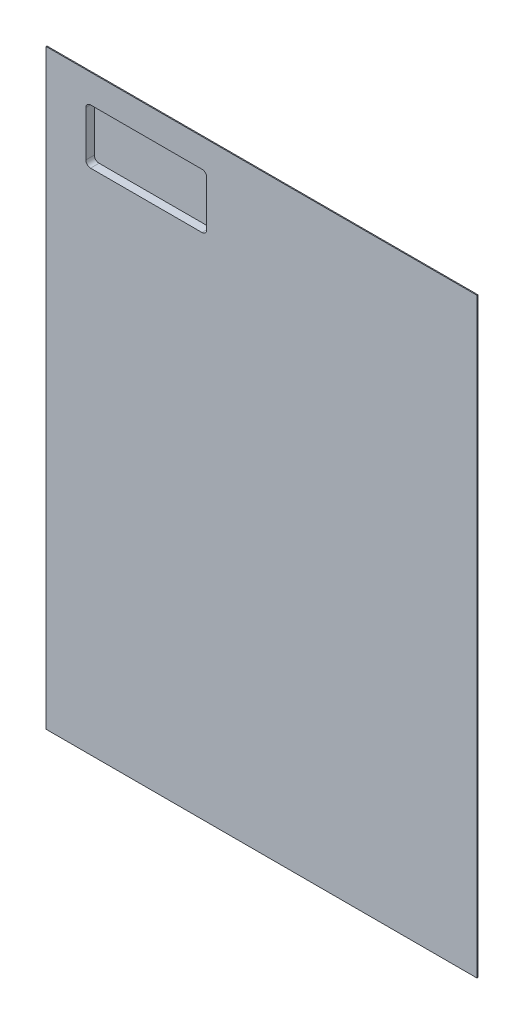
SolidWorks part; units mm, degrees
ref_plane "Front Plane" through (0, 0, 0) normal (0, 0, 1) x (1, 0, 0)
ref_plane "Top Plane" through (0, 0, 0) normal (0, 1, 0) x (1, 0, 0)
ref_plane "Right Plane" through (0, 0, 0) normal (1, 0, 0) x (0, 0, -1)
sketch "Sketch1" plane through (0, 0, 0) normal (0, 0, 1) x (1, 0, 0)
  line L1 (-228, 313) -> (228, 313)
  line L2 (-228, 313) -> (-228, -313)
  line L3 (-228, -313) -> (228, -313)
  line L4 (228, 313) -> (228, -313)
  line L5 (-228, 313) -> (228, -313) construction
  line L6 (-228, -313) -> (228, 313) construction
  point P0 (0, 0)
  dimension "D1" = 456
  dimension "D2" = 626
base flange "Base-Flange1" sketch "Sketch1" thickness 1 reverse thickness direction no parameters "D1"=0.7366
sketch "Sketch6" plane through (0, 0, 0) normal (0, 0, 1) x (1, 0, 0)
  line L0 (228, 313) -> (-228, 313) construction
  line L1 (-187, 284) -> (-57, 284)
  line L2 (-187, 284) -> (-187, 224)
  line L3 (-187, 224) -> (-57, 224)
  line L4 (-57, 284) -> (-57, 224)
  line L5 (-187, 284) -> (-57, 224) construction
  line L6 (-187, 224) -> (-57, 284) construction
  line L7 (-228, 313) -> (-228, -313) construction
  point P0 (-122, 254)
  dimension "D1" = 29
  dimension "D2" = 41
  dimension "D3" = 60
  dimension "D4" = 130
extrude "Boss-Extrude1" add sketch "Sketch6" against normal blind 10
sketch "Sketch7" plane through (0, 0, 0) normal (0, 0, 1) x (1, 0, 0)
  line L4 (-186, 283) -> (-58, 283)
  line L5 (-58, 283) -> (-58, 225)
  line L6 (-186, 225) -> (-58, 225)
  line L7 (-186, 283) -> (-186, 225)
  line L12 (-57, 284) -> (-57, 224) construction
  line L13 (-187, 224) -> (-57, 224) construction
  line L14 (-187, 284) -> (-187, 224) construction
  line L15 (-187, 284) -> (-57, 284) construction
  line L16 (-57, 284) -> (-57, 224) construction
  line L17 (-187, 224) -> (-57, 224) construction
  line L18 (-187, 284) -> (-187, 224) construction
  line L19 (-187, 284) -> (-57, 284) construction
  dimension "D1" = 1
extrude "Cut-Extrude2" cut sketch "Sketch7" against normal blind 1
shell "Shell2" thickness 1
fillet "Fillet1" radius 5 8 edges at (-57, 284, -5.5) (-57, 224, -5.5) (-187, 224, -5.5) (-187, 284, -5.5) (-186, 225, -4.5) (-186, 283, -4.5) (-58, 283, -4.5) (-58, 225, -4.5)
sketch "Bend-Lines1" plane through (0, 0, 0) normal (0, 1, 0) x (1, 0, 0)
sketch "Bounding-Box1" plane through (0, 0, 0) normal (0, 1, 0) x (1, 0, 0)
sheet metal parameters "Sheet-Metal1" thickness 1 parameters "D1"=0.7366
flat pattern "Flat-Pattern1"
sketch "Bend-Lines2" plane through (0, 0, 0) normal (0, 1, 0) x (1, 0, 0)
sketch3d "Bounding-Box2"
  line L0 (228, 313, 0) -> (228, -313, 0) construction
  line L1 (-228, 313, 0) -> (-228, -313, 0) construction
  line L2 (228, 313, 0) -> (-228, 313, 0) construction
  line L3 (228, -313, 0) -> (-228, -313, 0) construction
sheet metal parameters "Sheet-Metal2" thickness 1 parameters "D1"=0.7366
flat pattern "Flat-Pattern1"
sketch "Bend-Lines2" plane through (0, 0, 0) normal (0, 1, 0) x (1, 0, 0)
sketch3d "Bounding-Box2"
  line L0 (228, 313, 0) -> (228, -313, 0) construction
  line L1 (-228, 313, 0) -> (-228, -313, 0) construction
  line L2 (228, 313, 0) -> (-228, 313, 0) construction
  line L3 (228, -313, 0) -> (-228, -313, 0) construction
sheet metal parameters "Sheet-Metal4" thickness 1 parameters "D1"=0.7366
flat pattern "Flat-Pattern1"
sketch "Bend-Lines2" plane through (0, 0, 0) normal (0, 1, 0) x (1, 0, 0)
sketch3d "Bounding-Box2" [suppressed]
  line L0 (228, 313, 0) -> (228, -313, 0) construction
  line L1 (-228, 313, 0) -> (-228, -313, 0) construction
  line L2 (228, 313, 0) -> (-228, 313, 0) construction
  line L3 (228, -313, 0) -> (-228, -313, 0) construction
sheet metal parameters "Sheet-Metal6" thickness 1 parameters "D1"=0.7366
flat pattern "Flat-Pattern1"
sketch "Bend-Lines2" plane through (0, 0, 0) normal (0, 1, 0) x (1, 0, 0)
sketch3d "Bounding-Box2"
  line L0 (228, 313, 0) -> (228, -313, 0) construction
  line L1 (-228, 313, 0) -> (-228, -313, 0) construction
  line L2 (228, 313, 0) -> (-228, 313, 0) construction
  line L3 (228, -313, 0) -> (-228, -313, 0) construction
